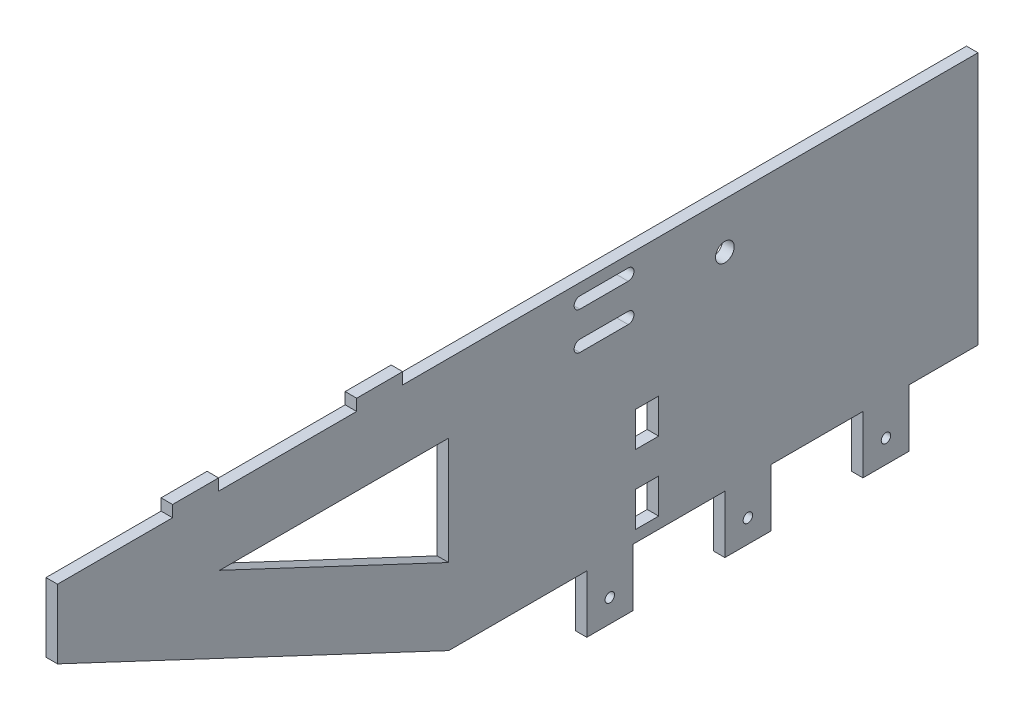
SolidWorks part; units mm, degrees
ref_plane "前基準面" through (0, 0, 0) normal (0, 0, 1) x (1, 0, 0)
ref_plane "上基準面" through (0, 0, 0) normal (0, 1, 0) x (1, 0, 0)
ref_plane "右基準面" through (0, 0, 0) normal (1, 0, 0) x (0, 0, -1)
sketch "草圖1" plane through (0, 0, 0) normal (1, 0, 0) x (0, 0, -1)
  line L1 (100, 55) -> (-100, 55)
  line L2 (100, 55) -> (100, -55)
  line L3 (100, -55) -> (-100, -55)
  line L4 (-100, 55) -> (-100, -55)
  line L5 (0, -55) -> (0, 55) construction
  line L6 (100, 0) -> (-100, 0) construction
  circle A0 centre (-10, 35) radius 4.05
  point P0 (0, 0)
  dimension "D3" = 8.1
  dimension "D1" = 200
  dimension "D2" = 110
  dimension "D4" = 90
  dimension "D5" = 90
extrude "填料-伸長1" add sketch "草圖1" along normal blind 5
sketch "草圖2" plane through (5, 0, 0) normal (1, 0, 0) x (0, 0, -1)
  line L0 (-100, -55) -> (100, -55) construction
  line L1 (-70, -55) -> (-50, -55)
  line L4 (-70, -55) -> (-70, -80)
  line L5 (-70, -80) -> (-50, -80)
  line L6 (-50, -80) -> (-50, -55)
  line L8 (-10, -55) -> (-10, -80)
  line L9 (-10, -80) -> (10, -80)
  line L10 (10, -80) -> (10, -55)
  line L12 (50, -55) -> (50, -80)
  line L13 (50, -80) -> (70, -80)
  line L14 (70, -80) -> (70, -55)
  line L17 (-100, 55) -> (-100, -55) construction
  line L18 (-70, -70) -> (70, -70) construction
  line L19 (-10, -55) -> (10, -55)
  line L20 (50, -55) -> (70, -55)
  line L21 (-70, -60) -> (70, -60) construction
  circle A0 centre (-60, -70) radius 2.05
  circle A1 centre (0, -70) radius 2.05
  circle A2 centre (60, -70) radius 2.05
  point P27 (-60, -80)
  point P30 (60, -80)
  point P32 (0, -55)
  dimension "D7" = 4.1
  dimension "D1" = 25
  dimension "D2" = 30
  dimension "D3" = 40
  dimension "D4" = 40
  dimension "D5" = 20
  dimension "D6" = 5
  dimension "D8" = 10
extrude "填料-伸長2" add sketch "草圖2" against normal blind 5
sketch "草圖3" plane through (5, 0, 0) normal (1, 0, 0) x (0, 0, -1)
  line L0 (-100, -55) -> (100, -55) construction
  line L1 (-100, 55) -> (-100, -55) construction
  line L2 (100, -55) -> (100, 55) construction
  line L4 (-100, 55) -> (-300, 55)
  line L5 (-300, 55) -> (-300, 25)
  line L6 (-300, 25) -> (-130, -55)
  line L7 (-130, -55) -> (-100, -55)
  line L8 (-100, 55) -> (-100, -55)
  line L9 (-130, 25) -> (-130, -21.8442)
  line L10 (-130, -21.8442) -> (-130, -21.8442)
  line L11 (-229.5439, 25) -> (-130, -21.8442)
  line L12 (-229.5439, 25) -> (-229.5439, 25)
  line L13 (-130, 25) -> (-229.5439, 25)
  line L14 (-100, -55) -> (-70, -55) construction
  dimension "D2" = 30
  dimension "D3" = 30
  dimension "D4" = 200
  dimension "D5" = 30
extrude "填料-伸長3" add sketch "草圖3" against normal blind 5
sketch "草圖4" plane through (5, 0, 0) normal (1, 0, 0) x (0, 0, -1)
  line L1 (-48.85, -4.8) -> (-38.75, -4.8)
  line L2 (-48.85, -4.8) -> (-48.85, -19.9)
  line L3 (-48.85, -19.9) -> (-38.75, -19.9)
  line L4 (-38.75, -4.8) -> (-38.75, -19.9)
  line L5 (-48.85, -34.9) -> (-38.75, -34.9)
  line L6 (-48.85, -34.9) -> (-48.85, -50)
  line L7 (-48.85, -50) -> (-38.75, -50)
  line L8 (-38.75, -34.9) -> (-38.75, -50)
  line L10 (-130, -55) -> (-70, -55) construction
  dimension "D1" = 81.15
  dimension "D3" = 10.1
  dimension "D4" = 15
  dimension "D5" = 15.1
  dimension "D6" = 5
extrude "除料-伸長1" cut sketch "草圖4" against normal through all
sketch "草圖5" plane through (0, 55, 0) normal (0, 1, 0) x (1, 0, 0)
  line L0 (0, -130) -> (5, -130) construction
  line L1 (0, -130) -> (5, -130) construction
  line L2 (0, 100) -> (0, -300) construction
  line L3 (0, -150) -> (5, -150)
  line L4 (0, -150) -> (0, -170)
  line L5 (0, -170) -> (5, -170)
  line L6 (5, -150) -> (5, -170)
  line L7 (5, 100) -> (5, -300) construction
  line L9 (0, -230) -> (5, -230)
  line L10 (0, -230) -> (0, -250)
  line L11 (0, -250) -> (5, -250)
  line L12 (5, -230) -> (5, -250)
  dimension "D1" = 20
  dimension "D2" = 60
  dimension "D3" = 20
extrude "填料-伸長4" add sketch "草圖5" along normal blind 5
sketch "草圖6" plane through (5, 0, 0) normal (1, 0, 0) x (0, 0, -1)
  line L0 (-73, 47.5) -> (-52, 47.5) construction
  line L1 (-73, 50) -> (-52, 50)
  line L2 (-73, 45) -> (-52, 45)
  line L3 (-73, 31.2) -> (-52, 31.2) construction
  line L4 (-73, 33.7) -> (-52, 33.7)
  line L5 (-73, 28.7) -> (-52, 28.7)
  line L6 (100, 55) -> (-150, 55) construction
  line L7 (-80, 55) -> (-45, 55) construction
  line L8 (-80, 55) -> (-80, 20) construction
  line L9 (-80, 20) -> (-45, 20) construction
  line L10 (-45, 55) -> (-45, 20) construction
  arc A0 (-73, 50) -> (-73, 45) centre (-73, 47.5) ccw
  arc A1 (-52, 45) -> (-52, 50) centre (-52, 47.5) ccw
  arc A2 (-73, 33.7) -> (-73, 28.7) centre (-73, 31.2) ccw
  arc A3 (-52, 28.7) -> (-52, 33.7) centre (-52, 31.2) ccw
  arc A4 (-73, 50) -> (-73, 45) centre (-73, 47.5) cw construction
  arc A5 (-52, 50) -> (-52, 45) centre (-52, 47.5) ccw construction
  point P2 (-62.5, 47.5)
  point P7 (-62.5, 31.2)
  point P16 (-70.5, 47.5)
  point P19 (-54.5, 47.5)
  point P20 (0, 0)
  point P21 (-62.5, 55)
  point P22 (-79.5806, 45.8714)
  point P27 (-65.2021, 32.0201)
  point P30 (-67.3442, 36.2)
  dimension "D1" = 5
  dimension "D2" = 16
  dimension "D3" = 11.3
  dimension "D4" = 35
  dimension "D5" = 5
  dimension "D6" = 35
  dimension "D7" = 50
extrude "除料-伸長2" cut sketch "草圖6" against normal through all
